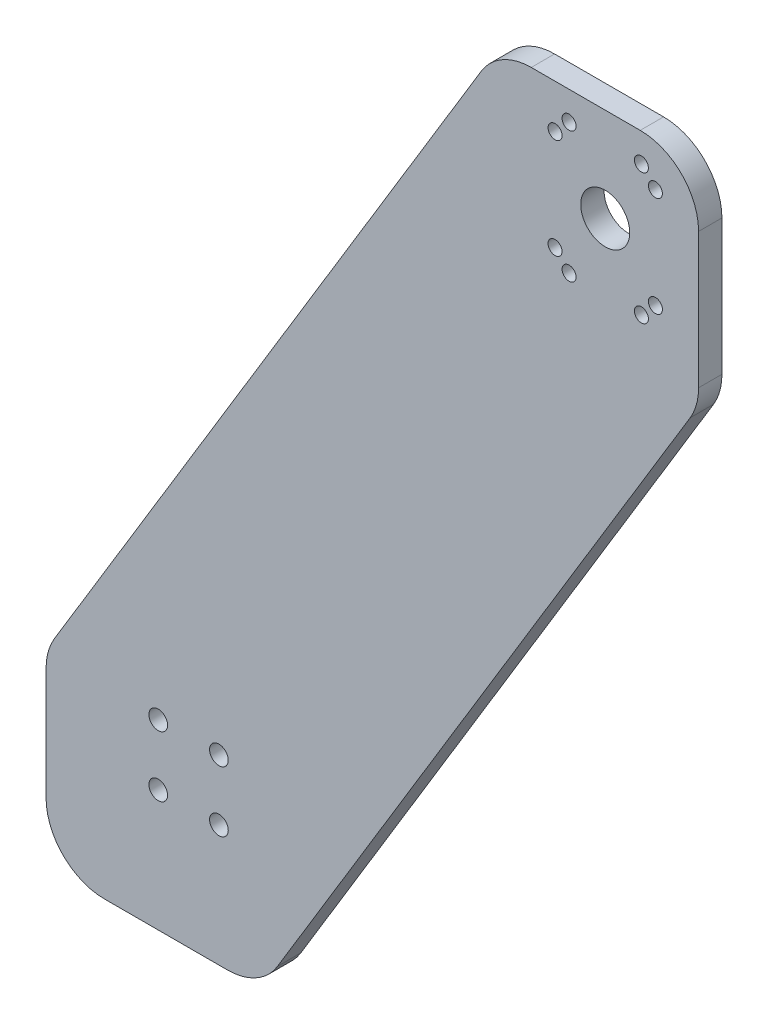
SolidWorks part; units mm, degrees
ref_plane "Piano frontale" through (0, 0, 0) normal (0, 0, 1) x (1, 0, 0)
ref_plane "Piano superiore" through (0, 0, 0) normal (0, 1, 0) x (1, 0, 0)
ref_plane "Piano destro" through (0, 0, 0) normal (1, 0, 0) x (0, 0, -1)
sketch "Schizzo1" plane through (0, 0, 0) normal (0, 0, 1) x (1, 0, 0)
  line L0 (25, 0) -> (77.7546, 0)
  line L1 (99.1387, 12.0493) -> (275.9682, 304.0295)
  line L2 (279.5841, 316.9801) -> (279.5841, 375)
  line L3 (254.5841, 400) -> (207.8857, 400)
  line L4 (0, 73.0199) -> (0, 25)
  line L5 (186.5016, 387.9507) -> (3.6159, 85.9705)
  line L6 (261.6765, 396.2552) -> (-22.3051, -72.6542) construction
  line L7 (20.2808, 65) -> (116.5802, 65) construction
  line L8 (61.0612, 65) -> (61.0612, 110.084) construction
  line L9 (239.5841, 359.7762) -> (211.0935, 388.2668) construction
  line L10 (239.5841, 359.7762) -> (201.235, 359.7762) construction
  line L11 (239.5841, 359.7762) -> (239.5841, 402.6918) construction
  line L13 (255.0841, 331.7762) -> (224.0841, 331.7762) construction
  line L14 (255.0841, 331.7762) -> (255.0841, 387.7762) construction
  line L15 (255.0841, 387.7762) -> (224.0841, 387.7762) construction
  line L16 (224.0841, 331.7762) -> (224.0841, 387.7762) construction
  line L17 (255.0841, 331.7762) -> (224.0841, 387.7762) construction
  line L18 (255.0841, 387.7762) -> (224.0841, 331.7762) construction
  circle A0 centre (48.0612, 78) radius 4
  circle A1 centre (74.0612, 78) radius 4
  circle A2 centre (74.0612, 52) radius 4
  circle A3 centre (48.0612, 52) radius 4
  circle A4 centre (239.5841, 359.7762) radius 10.5
  circle A5 centre (239.5841, 359.7762) radius 30.41 construction
  arc A6 (99.1387, 12.0493) -> (77.7546, 0) centre (77.7546, 25) cw
  arc A7 (25, 0) -> (0, 25) centre (25, 25) cw
  arc A8 (0, 73.0199) -> (3.6159, 85.9705) centre (25, 73.0199) cw
  arc A9 (279.5841, 316.9801) -> (275.9682, 304.0295) centre (254.5841, 316.9801) cw
  arc A10 (279.5841, 375) -> (254.5841, 400) centre (254.5841, 375) ccw
  arc A11 (207.8857, 400) -> (186.5016, 387.9507) centre (207.8857, 375) ccw
  circle A12 centre (224.0841, 387.7762) radius 3
  circle A13 centre (255.0841, 387.7762) radius 3
  circle A14 centre (261.0872, 381.2793) radius 3
  circle A15 centre (261.0872, 338.2731) radius 3
  circle A16 centre (255.0841, 331.7762) radius 3
  circle A17 centre (224.0841, 331.7762) radius 3
  circle A18 centre (218.0809, 338.2731) radius 3
  circle A19 centre (218.0809, 381.2793) radius 3
  point P27 (218.0809, 381.2793)
  point P28 (261.0872, 381.2793)
  point P29 (261.0872, 338.2731)
  point P30 (218.0809, 338.2731)
  point P39 (0, 0)
  point P42 (0, 80)
  point P45 (279.5841, 310)
  point P48 (279.5841, 400)
  dimension "D6" = 8
  dimension "D7" = 13
  dimension "D9" = 21
  dimension "D11" = 45
  dimension "D14" = 25
  dimension "D15" = 6
  dimension "D16" = 65
  dimension "D1" = 121.2
  dimension "D2" = 120
  dimension "D3" = 80
  dimension "D4" = 400
  dimension "D5" = 90
  dimension "D8" = 13
  dimension "D10" = 40
  dimension "D12" = 31
  dimension "D13" = 56
extrude "Estrusione-Estrusione2" add sketch "Schizzo1" against normal blind 10
sketch "Schizzo2" plane through (0, 0, 0) normal (0, -1, 0) x (1, 0, 0)
  line L0 (25, -5) -> (77.7546, -5) construction
  line L1 (25, -10) -> (25, 0) construction
  line L2 (77.7546, -10) -> (77.7546, 0) construction
  line L3 (51.3773, -5) -> (51.3773, 0) construction
  line L4 (25, 0) -> (77.7546, 0) construction
  circle A0 centre (51.3773, -5) radius 2
  circle A1 centre (78.8773, -5) radius 2
  circle A2 centre (23.8773, -5) radius 2
  dimension "D1" = 4
  dimension "D2" = 27.5
extrude "Taglio-Estrusione1" cut sketch "Schizzo2" against normal blind 15
